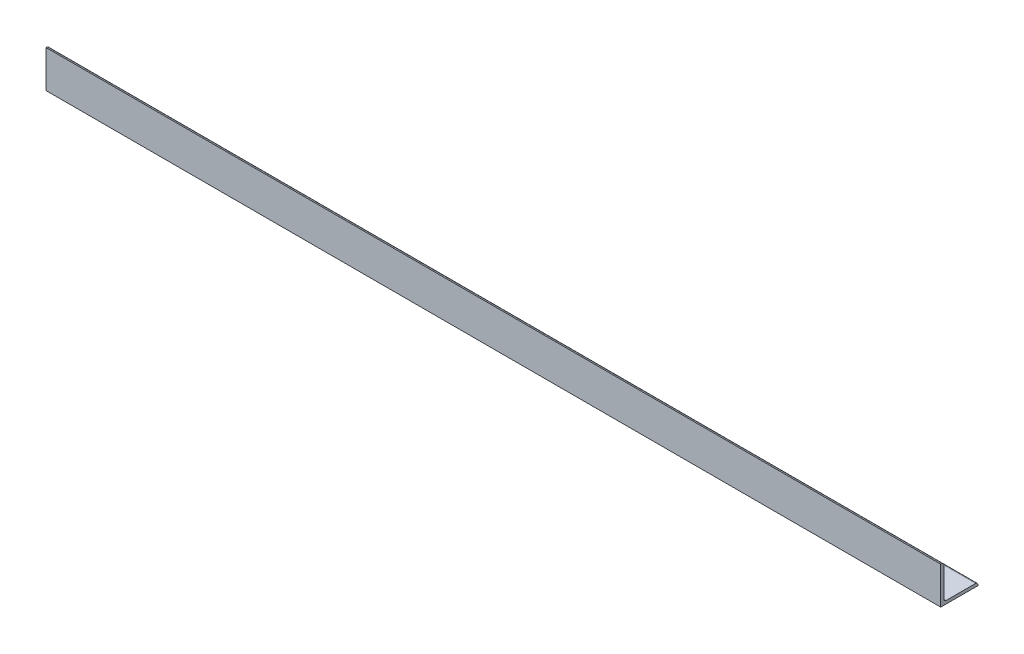
SolidWorks part; units mm, degrees
material "6063-T6"
ref_plane "Front Plane" through (0, 0, 0) normal (0, 0, 1) x (1, 0, 0)
ref_plane "Top Plane" through (0, 0, 0) normal (0, 1, 0) x (1, 0, 0)
ref_plane "Right Plane" through (0, 0, 0) normal (1, 0, 0) x (0, 0, -1)
sketch "Sketch1" plane through (0, 0, 0) normal (1, 0, 0) x (0, 0, -1)
  line L0 (0, 76.2) -> (0, 0)
  line L1 (0, 0) -> (76.2, 0)
  line L2 (6.35, 71.12) -> (6.35, 11.43)
  line L3 (11.43, 6.35) -> (71.12, 6.35)
  line L4 (0, 76.2) -> (1.27, 76.2)
  line L5 (76.2, 1.27) -> (76.2, 0)
  line L6 (6.35, 76.2) -> (6.35, 6.35) construction
  line L7 (6.35, 6.35) -> (76.2, 6.35) construction
  arc A0 (6.35, 11.43) -> (11.43, 6.35) centre (11.43, 11.43) ccw
  arc A1 (71.12, 6.35) -> (76.2, 1.27) centre (71.12, 1.27) cw
  arc A2 (6.35, 71.12) -> (1.27, 76.2) centre (1.27, 71.12) ccw
  dimension "D1" = 76.2
  dimension "D3" = 5.08
  dimension "D2" = 6.35
extrude "Boss-Extrude1" add sketch "Sketch1" along normal blind 914.4 and the other way blind 914.4
